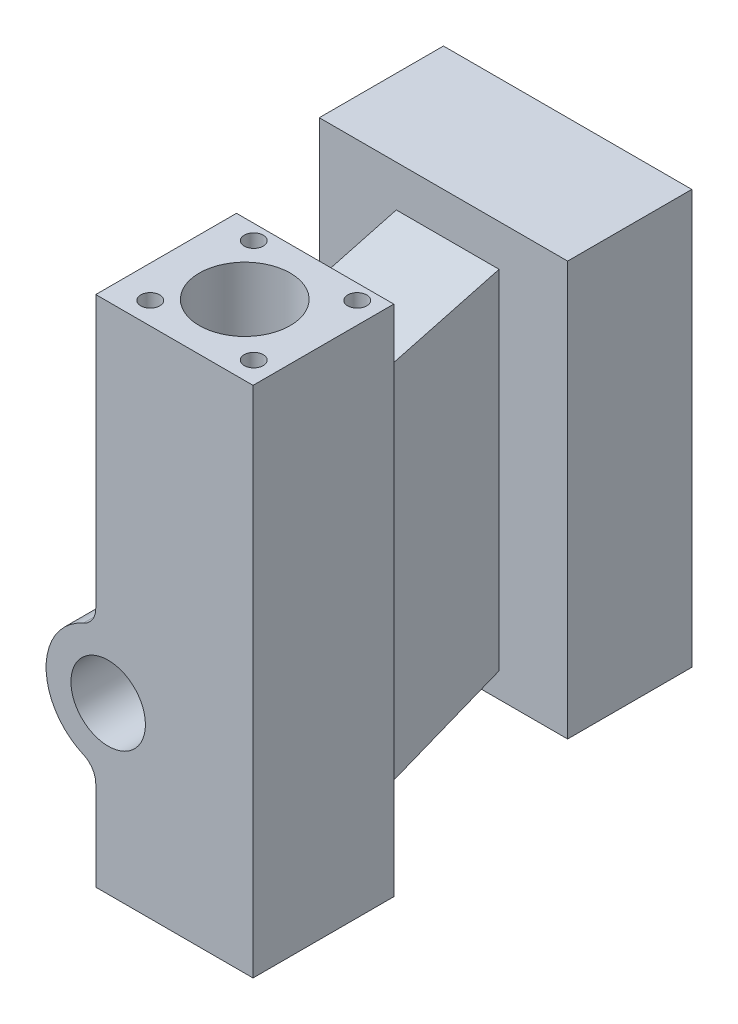
SolidWorks part; units mm, degrees
ref_plane "Front Plane" through (0, 0, 0) normal (0, 0, 1) x (1, 0, 0)
ref_plane "Top Plane" through (0, 0, 0) normal (0, 1, 0) x (1, 0, 0)
ref_plane "Right Plane" through (0, 0, 0) normal (1, 0, 0) x (0, 0, -1)
sketch "Sketch1" plane through (0, 0, 0) normal (0, 0, 1) x (1, 0, 0)
  line L1 (-26.1812, 49.3094) -> (11.8188, 49.3094)
  line L2 (-26.1812, 49.3094) -> (-26.1812, -74.6906)
  line L3 (-26.1812, -74.6906) -> (11.8188, -74.6906)
  line L4 (11.8188, 49.3094) -> (11.8188, -74.6906)
  dimension "D1" = 124
  dimension "D2" = 38
extrude "Boss-Extrude1" add sketch "Sketch1" along normal blind 34
sketch "Sketch2" plane through (0, 0, 34) normal (0, 0, 1) x (1, 0, 0)
  line L4 (11.8188, -74.6906) -> (11.8188, 49.3094) construction
  line L5 (-26.1812, -74.6906) -> (11.8188, -74.6906) construction
  circle A0 centre (-23.1812, -34.6906) radius 15
  dimension "D1" = 35
  dimension "D2" = 40
extrude "Boss-Extrude2" add sketch "Sketch2" against normal blind 34
fillet "Fillet1" radius 5 2 edges at (-26.1812, -49.3876, 17) (-26.1812, -19.9937, 17)
sketch "Sketch3" plane through (0, -74.6906, 0) normal (0, -1, 0) x (1, 0, 0)
  line L0 (11.8188, 34) -> (11.8188, 0) construction
  line L1 (-26.1812, 34) -> (11.8188, 34) construction
  circle A0 centre (-7.1812, 17) radius 11
  dimension "D1" = 19
  dimension "D2" = 17
extrude "Cut-Extrude1" cut sketch "Sketch3" against normal blind 1000
sketch "Sketch4" plane through (0, 0, 34) normal (0, 0, 1) x (1, 0, 0)
  circle A0 centre (-23.1812, -34.6906) radius 9
  arc A1 (-29.1812, -20.9429) -> (-29.1812, -48.4384) centre (-23.1812, -34.6906) ccw construction
  dimension "D1" = 18
sketch "Sketch5" plane through (0, 0, 0) normal (0, 0, -1) x (-1, 0, 0)
  line L1 (-7.2618, 48.6909) -> (17.5691, 48.6909)
  line L2 (-7.2618, 48.6909) -> (-7.2618, -62.513)
  line L3 (-7.2618, -62.513) -> (17.5691, -62.513)
  line L4 (17.5691, 48.6909) -> (17.5691, -62.513)
extrude "Boss-Extrude3" add sketch "Sketch5" along normal blind 30
sketch "Sketch6" plane through (0, 0, -30) normal (0, 0, -1) x (-1, 0, 0)
  line L0 (26.1812, 49.3094) -> (26.1812, -16.3603) construction
  line L1 (-23.8188, 49.3094) -> (36.1812, 49.3094)
  line L2 (-23.8188, 49.3094) -> (-23.8187, -50.6906)
  line L3 (-23.8187, -50.6906) -> (36.1812, -50.6906)
  line L4 (36.1812, 49.3094) -> (36.1812, -50.6906)
  line L5 (-11.8188, 49.3094) -> (26.1812, 49.3094) construction
  dimension "D1" = 60
  dimension "D2" = 100
  dimension "D3" = 10
extrude "Boss-Extrude4" add sketch "Sketch6" along normal blind 30
sketch "Sketch9" plane through (7.2618, 0, 0) normal (1, 0, 0) x (0, 0, -1)
  line L0 (0, 52.6027) -> (0, 31.3094)
  line L1 (0, 31.3094) -> (30, 39.3094)
  line L2 (30, 39.3094) -> (30, 52.6027)
  line L3 (30, 52.6027) -> (0, 52.6027)
  line L4 (0, -56.6906) -> (0, -66.3738)
  line L5 (0, -66.3738) -> (30, -69.2814)
  line L6 (30, -69.2814) -> (30, -44.6906)
  line L7 (30, -44.6906) -> (0, -56.6906)
  line L8 (30, -50.6906) -> (30, 48.6909) construction
  line L9 (0, 49.3094) -> (0, -16.3603) construction
  line L10 (30, -50.6906) -> (30, 49.3094) construction
  line L11 (60, 49.3094) -> (30, 49.3094) construction
  line L12 (-34, 49.3094) -> (0, 49.3094) construction
  line L13 (60, -50.6906) -> (30, -50.6906) construction
  line L14 (-34, -74.6906) -> (0, -74.6906) construction
  dimension "D1" = 10
  dimension "D2" = 18
  dimension "D3" = 6
  dimension "D4" = 18
extrude "Cut-Extrude5" cut sketch "Sketch9" against normal blind 100
sketch "Sketch10" plane through (-36.1812, 0, 0) normal (-1, 0, 0) x (0, 0, 1)
  line L0 (-60, -50.6906) -> (-60, 49.3094) construction
  line L1 (-60, -50.6906) -> (-30, -50.6906) construction
  circle A0 centre (-45, -15.6906) radius 7.5
  dimension "D3" = 15
  dimension "D1" = 15
  dimension "D2" = 35
extrude "Cut-Extrude6" cut sketch "Sketch10" against normal blind 10
sketch "Sketch11" plane through (0, 49.3094, 0) normal (0, 1, 0) x (1, 0, 0)
  circle A0 centre (6.6247, -28.639) radius 2.3015
extrude "Cut-Extrude7" cut sketch "Sketch11" against normal blind 10
pattern_linear "LPattern1" count 2 spacing 25 along (-1, 0, 0) count 2 spacing 25 along (0, 0, -1) of "Cut-Extrude7"
extrude "Вырез-Вытянуть1" cut sketch "Sketch4" against normal blind 17
